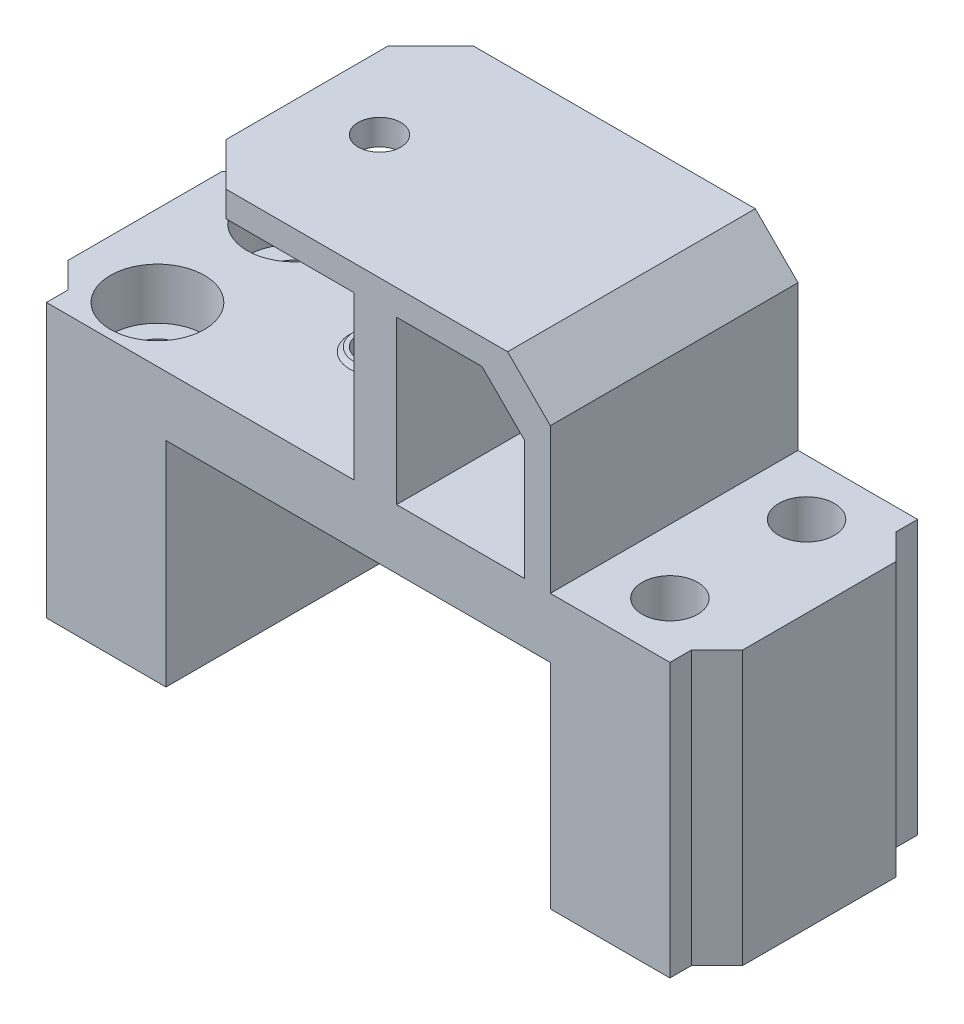
SolidWorks part; units mm, degrees
ref_plane "Front Plane" through (0, 0, 0) normal (0, 0, 1) x (1, 0, 0)
ref_plane "Top Plane" through (0, 0, 0) normal (0, 1, 0) x (1, 0, 0)
ref_plane "Right Plane" through (0, 0, 0) normal (1, 0, 0) x (0, 0, -1)
sketch "Sketch1" plane through (0, 0, 0) normal (0, 1, 0) x (1, 0, 0)
  line L0 (66.5, -1) -> (66.5, 17)
  line L8 (110.5518, 17) -> (110.5518, -1)
  line L9 (86.5, 16) -> (86.5, 0) construction
  line L10 (66.5, 16) -> (86.5, 16) construction
  line L12 (66.5, 17) -> (110.5518, 17)
  line L15 (110.5518, -1) -> (66.5, -1)
  line L21 (99.7369, 8) -> (95.7369, 8) construction
  line L22 (99.7369, 5.75) -> (95.7369, 5.75)
  line L23 (99.7369, 10.25) -> (95.7369, 10.25)
  arc A8 (99.7369, 5.75) -> (99.7369, 10.25) centre (99.7369, 8) ccw
  arc A9 (95.7369, 10.25) -> (95.7369, 5.75) centre (95.7369, 8) ccw
  point P0 (86.5, 8)
  point P1 (66.5, 8)
  point P39 (97.7369, 8)
  dimension "D2" = 16
  dimension "D3" = 11.2369
  dimension "D4" = 0
  dimension "D5" = 18
  dimension "D6" = 0
  dimension "D8" = 20
extrude "Boss-Extrude1" add sketch "Sketch1" along normal blind 1.5
sketch "Sketch2" plane through (0, 1.5, 0) normal (0, 1, 0) x (1, 0, 0)
  line L0 (66.5, -1) -> (110.5518, -1) construction
  line L1 (66.5, 17) -> (69.5, 17)
  line L2 (66.5, 17) -> (66.5, -1)
  line L3 (66.5, -1) -> (69.5, -1)
  line L4 (69.5, 17) -> (69.5, -1)
  dimension "D1" = 3
extrude "Boss-Extrude2" add sketch "Sketch2" along normal blind 13
sketch "Sketch3" plane through (66.5, 0, 0) normal (-1, 0, 0) x (0, 0, 1)
  line L0 (-17, 14.5) -> (1, 14.5) construction
  line L1 (-22.5, 14.5) -> (6.5, 14.5)
  line L2 (-22.5, 14.5) -> (-22.5, 11.5)
  line L3 (-22.5, 11.5) -> (6.5, 11.5)
  line L4 (6.5, 14.5) -> (6.5, 11.5)
  line L5 (-22.5, 14.5) -> (6.5, 11.5) construction
  line L6 (-22.5, 11.5) -> (6.5, 14.5) construction
  line L7 (-17, 0) -> (1, 0) construction
  point P0 (-8, 13)
  point P10 (-8, 0)
  dimension "D1" = 3
  dimension "D2" = 29
extrude "Boss-Extrude3" add sketch "Sketch3" along normal blind 14
chamfer "Chamfer1" distance 3 angle 45 2 edges at (66.5, 13, 1) (66.5, 13, -17)
sketch "Sketch4" plane through (0, 14.5, 0) normal (0, 1, 0) x (1, 0, 0)
  line L0 (60, 22.5) -> (60, 16) construction
  line L1 (52.5, 22.5) -> (66.5, 22.5) construction
  line L2 (60, 16) -> (60, 0) construction
  line L3 (60, 0) -> (60, -6.5) construction
  line L4 (52.5, -6.5) -> (66.5, -6.5) construction
  line L5 (66.5, 17) -> (66.5, -1) construction
  circle A0 centre (60, 16) radius 3.25
  circle A1 centre (60, 0) radius 3.25
  dimension "D2" = 6.5
  dimension "D1" = 16
  dimension "D3" = 6.5
extrude "Cut-Extrude1" cut sketch "Sketch4" against normal blind 14
sketch "Sketch5" plane through (0, 14.5, 0) normal (0, 1, 0) x (1, 0, 0)
  line L8 (69.5, -1) -> (69.5, 17)
  line L9 (69.5, 17) -> (66.5, 20)
  line L10 (66.5, 20) -> (66.5, 22.5)
  line L11 (66.5, 22.5) -> (52.5, 22.5)
  line L12 (52.5, 22.5) -> (52.5, -6.5)
  line L13 (52.5, -6.5) -> (66.5, -6.5)
  line L14 (66.5, -6.5) -> (66.5, -4)
  line L15 (66.5, -4) -> (69.5, -1)
  line L16 (69.5, -1) -> (69.5, 17)
  line L17 (69.5, 17) -> (66.5, 20)
  line L18 (66.5, 20) -> (66.5, 22.5)
  line L19 (66.5, 22.5) -> (52.5, 22.5)
  line L20 (52.5, 22.5) -> (52.5, -6.5)
  line L21 (52.5, -6.5) -> (66.5, -6.5)
  line L22 (66.5, -6.5) -> (66.5, -4)
  line L23 (66.5, -4) -> (69.5, -1)
  circle A0 centre (60, 16) radius 3.25
  circle A1 centre (60, 0) radius 3.25
  dimension "D1" = 0
extrude "Boss-Extrude4" add sketch "Sketch5" along normal blind 20
ref_plane "Plane1" through (22.5, 0, 0) normal (-1, 0, 0) x (0, 0, 1)
sketch "Sketch6" plane through (0, 34.5, 0) normal (0, 1, 0) x (1, 0, 0)
  line L0 (52.5, 22.5) -> (7.5, 22.5)
  line L1 (30, 22.5) -> (30, -6.5)
  line L2 (7.5, -6.5) -> (52.5, -6.5)
  line L3 (7.5, -6.5) -> (-6.5, -6.5)
  line L4 (-6.5, -6.5) -> (-6.5, -4)
  line L5 (-6.5, -4) -> (-9.5, -1)
  line L6 (-9.5, -1) -> (-9.5, 17)
  line L7 (-9.5, 17) -> (-6.5, 20)
  line L8 (66.5, -4) -> (69.5, -1)
  line L9 (69.5, -1) -> (69.5, 17)
  line L10 (69.5, 17) -> (66.5, 20)
  line L11 (66.5, 20) -> (66.5, 22.5)
  line L12 (66.5, 22.5) -> (52.5, 22.5)
  line L13 (52.5, 22.5) -> (52.5, -6.5)
  line L14 (52.5, -6.5) -> (66.5, -6.5)
  line L15 (66.5, -6.5) -> (66.5, -4)
  line L16 (66.5, -4) -> (69.5, -1)
  line L17 (69.5, -1) -> (69.5, 17)
  line L18 (69.5, 17) -> (66.5, 20)
  line L19 (66.5, 20) -> (66.5, 22.5)
  line L20 (66.5, 22.5) -> (52.5, 22.5)
  line L21 (-6.5, 20) -> (-6.5, 22.5)
  line L22 (52.5, -6.5) -> (66.5, -6.5)
  line L23 (66.5, -6.5) -> (66.5, -4)
  line L24 (-6.5, 22.5) -> (7.5, 22.5)
  circle A0 centre (60, 16) radius 3.25
  circle A1 centre (60, 0) radius 3.25
  circle A2 centre (0, 16) radius 3.25
  circle A3 centre (0, 0) radius 3.25
  circle M12 centre (60, 16) radius 3.25
  line M13 (66.5, -4) -> (69.5, -1)
  line M14 (69.5, -1) -> (69.5, 17)
  line M15 (69.5, 17) -> (66.5, 20)
  line M16 (66.5, 20) -> (66.5, 22.5)
  line M17 (66.5, 22.5) -> (52.5, 22.5)
  line M18 (52.5, 22.5) -> (52.5, -6.5)
  line M19 (52.5, -6.5) -> (66.5, -6.5)
  line M20 (66.5, -6.5) -> (66.5, -4)
  circle M21 centre (60, 0) radius 3.25
  dimension "D2" = 30
  dimension "D1" = 0
extrude "Boss-Extrude5" add sketch "Sketch6" along normal blind 7 contours L24 L21 L7 L6 L5 L4 L3 L2 L1 L0 A2 A3 | L1 L2 L0 M18 | M20 M13 M14 M15 M16 M17 M18 M19 M21 M12 region at (41.25, 34.5, -8) region at (60.7364, 34.5, -8) region at (11.3141, 34.5, -8)
sketch "Sketch8" plane through (0, 34.5, 0) normal (0, -1, 0) x (1, 0, 0)
  line L0 (7.5, 6.5) -> (7.5, -22.5)
  line L8 (-6.5, -22.5) -> (52.5, -22.5)
  line L9 (52.5, -22.5) -> (52.5, 6.5)
  line L10 (52.5, 6.5) -> (-6.5, 6.5)
  line L11 (-6.5, 6.5) -> (-6.5, 4)
  line L12 (-6.5, 4) -> (-9.5, 1)
  line L13 (-9.5, 1) -> (-9.5, -17)
  line L14 (-9.5, -17) -> (-6.5, -20)
  line L15 (-6.5, -20) -> (-6.5, -22.5)
  line L16 (-6.5, -22.5) -> (7.5, -22.5)
  line L17 (52.5, -22.5) -> (52.5, 6.5)
  line L18 (7.5, 6.5) -> (-6.5, 6.5)
  line L19 (-6.5, 6.5) -> (-6.5, 4)
  line L20 (-6.5, 4) -> (-9.5, 1)
  line L21 (-9.5, 1) -> (-9.5, -17)
  line L22 (-9.5, -17) -> (-6.5, -20)
  line L23 (-6.5, -20) -> (-6.5, -22.5)
  circle A0 centre (0, 0) radius 3.25
  circle A1 centre (0, -16) radius 3.25
  circle M10 centre (0, 0) radius 3.25
  circle M11 centre (0, -16) radius 3.25
  line M12 (-6.5, -22.5) -> (52.5, -22.5)
  line M14 (52.5, 6.5) -> (-6.5, 6.5)
  line M15 (-6.5, 6.5) -> (-6.5, 4)
  line M16 (-6.5, 4) -> (-9.5, 1)
  line M17 (-9.5, 1) -> (-9.5, -17)
  line M18 (-9.5, -17) -> (-6.5, -20)
  line M19 (-6.5, -20) -> (-6.5, -22.5)
  dimension "D2" = 14
  dimension "D1" = 0
extrude "Boss-Extrude6" add sketch "Sketch8" along normal up to surface (23 mm away) contours L0 M14 M15 M16 M17 M18 M19 M12 M11 M10 region at (-0.7364, 34.5, -8) up to face at (60, 11.5, 3.25)
sketch "Sketch18" plane through (0, 0, 6.5) normal (0, 0, 1) x (1, 0, 0)
  line L0 (9.5, 60.5) -> (29.5, 60.5)
  line L1 (29.5, 60.5) -> (29.5, 41.5)
  line L2 (66.5, 41.5) -> (-6.5, 41.5) construction
  line L3 (9.5, 60.5) -> (9.5, 63.5)
  line L4 (9.5, 63.5) -> (34.5, 63.5)
  line L5 (34.5, 63.5) -> (34.5, 41.5)
  line L6 (34.5, 41.5) -> (29.5, 41.5)
  dimension "D1" = 19
  dimension "D2" = 3
  dimension "D3" = 5
  dimension "D4" = 32
  dimension "D5" = 25
extrude "Boss-Extrude8" add sketch "Sketch18" against normal blind 29
sketch "Sketch9" plane through (0, 0, 0) normal (0, -1, 0) x (-1, 0, 0)
  circle A0 centre (-87.7208, 8.662) radius 38.7198
extrude "Cut-Extrude2" cut sketch "Sketch9" against normal up to surface (11.5 mm away) up to face at (0, 11.5, 3.25)
sketch "Sketch10" plane through (0, 41.5, 0) normal (0, 1, 0) x (1, 0, 0)
  line L0 (30, 22.5) -> (30, -6.5) construction
  line L1 (-6.5, 22.5) -> (29.5, 22.5) construction
  line L2 (66.5, -6.5) -> (34.5, -6.5) construction
  circle A0 centre (18, 8) radius 2.5
  dimension "D2" = 5
  dimension "D1" = 12
extrude "Cut-Extrude3" cut sketch "Sketch10" against normal through all both and the other way through all
sketch "Sketch11" plane through (0, 34.5, 0) normal (0, -1, 0) x (-1, 0, 0)
  line L1 (-18, 3.3812) -> (-14, 5.6906)
  line L2 (-14, 5.6906) -> (-14, 10.3094)
  line L3 (-14, 10.3094) -> (-18, 12.6188)
  line L4 (-18, 12.6188) -> (-22, 10.3094)
  line L5 (-22, 10.3094) -> (-22, 5.6906)
  line L6 (-22, 5.6906) -> (-18, 3.3812)
  circle A0 centre (-18, 8) radius 4 construction
  dimension "D1" = 8
extrude "Cut-Extrude4" cut sketch "Sketch11" against normal blind 3
sketch "Sketch12" plane through (0, 41.5, 0) normal (0, 1, 0) x (1, 0, 0)
  circle A0 centre (18, 8) radius 2.5
  circle A1 centre (18, 8) radius 3
  dimension "D1" = 6
extrude "Boss-Extrude7" add sketch "Sketch12" along normal blind 0.5
chamfer "Chamfer2" distance 0.5 angle 45 1 edges at (18, 41.5, -5)
sketch "Sketch17" plane through (0, 41.5, 0) normal (0, 1, 0) x (1, 0, 0)
  circle A0 centre (0, 16) radius 5.5
  circle A1 centre (0, 0) radius 5.5
  dimension "D1" = 11
  dimension "D2" = 11
extrude "Cut-Extrude5" cut sketch "Sketch17" against normal blind 6
chamfer "Chamfer3" distance 5 angle 45 2 edges at (9.5, 62, -22.5) (9.5, 62, 6.5)
sketch "Sketch19" plane through (0, 0, 6.5) normal (0, 0, 1) x (1, 0, 0)
  line L0 (34.5, 63.5) -> (52.5, 63.5)
  line L1 (52.5, 63.5) -> (52.5, 41.5)
  line L2 (66.5, 41.5) -> (34.5, 41.5) construction
  line L3 (52.5, 41.5) -> (49.5, 41.5)
  line L4 (49.5, 41.5) -> (49.5, 60.5)
  line L5 (49.5, 60.5) -> (29.5, 60.5)
  line L6 (29.5, 60.5) -> (34.5, 63.5)
  line L7 (34.5, 41.5) -> (34.5, 63.5) construction
  dimension "D1" = 3
  dimension "D2" = 15
extrude "Boss-Extrude9" add sketch "Sketch19" against normal up to surface (29 mm away) up to face at (28.3571, 37.7857, -22.5)
chamfer "Chamfer4" distance 5 angle 45 2 edges at (52.5, 63.5, -8) (49.5, 60.5, -8)
sketch "Sketch20" plane through (0, 11.5, 0) normal (0, -1, 0) x (1, 0, 0)
  line L0 (66.5, -20) -> (69.5, -17) construction
  line L1 (69.5, -17) -> (69.5, 1) construction
  line L2 (69.5, 1) -> (66.5, 4) construction
  line L3 (66.5, 4) -> (66.5, 6.5) construction
  line L4 (66.5, 6.5) -> (52.5, 6.5) construction
  line L5 (52.5, 6.5) -> (52.5, -22.5) construction
  line L6 (52.5, -22.5) -> (66.5, -22.5) construction
  line L7 (66.5, -22.5) -> (66.5, -20) construction
  line L8 (7.5, -22.5) -> (7.5, 6.5) construction
  line L9 (7.5, 6.5) -> (-6.5, 6.5) construction
  line L10 (-6.5, 6.5) -> (-6.5, 4) construction
  line L11 (-6.5, 4) -> (-9.5, 1) construction
  line L12 (-9.5, 1) -> (-9.5, -17) construction
  line L13 (-9.5, -17) -> (-6.5, -20) construction
  line L14 (-6.5, -20) -> (-6.5, -22.5) construction
  line L15 (-6.5, -22.5) -> (7.5, -22.5) construction
  line L16 (66.5, -20) -> (69.5, -17)
  line L17 (69.5, -17) -> (69.5, 1)
  line L18 (69.5, 1) -> (66.5, 4)
  line L19 (66.5, 4) -> (66.5, 6.5)
  line L20 (66.5, 6.5) -> (52.5, 6.5)
  line L21 (52.5, 6.5) -> (52.5, -22.5)
  line L22 (52.5, -22.5) -> (66.5, -22.5)
  line L23 (66.5, -22.5) -> (66.5, -20)
  line L24 (7.5, -22.5) -> (7.5, 6.5)
  line L25 (7.5, 6.5) -> (-6.5, 6.5)
  line L26 (-6.5, 6.5) -> (-6.5, 4)
  line L27 (-6.5, 4) -> (-9.5, 1)
  line L28 (-9.5, 1) -> (-9.5, -17)
  line L29 (-9.5, -17) -> (-6.5, -20)
  line L30 (-6.5, -20) -> (-6.5, -22.5)
  line L31 (-6.5, -22.5) -> (7.5, -22.5)
  circle A0 centre (0, 0) radius 3.25
  circle A1 centre (0, -16) radius 3.25
  circle A2 centre (60, 0) radius 3.25
  circle A3 centre (60, -16) radius 3.25
extrude "Boss-Extrude10" add sketch "Sketch20" along normal blind 2
